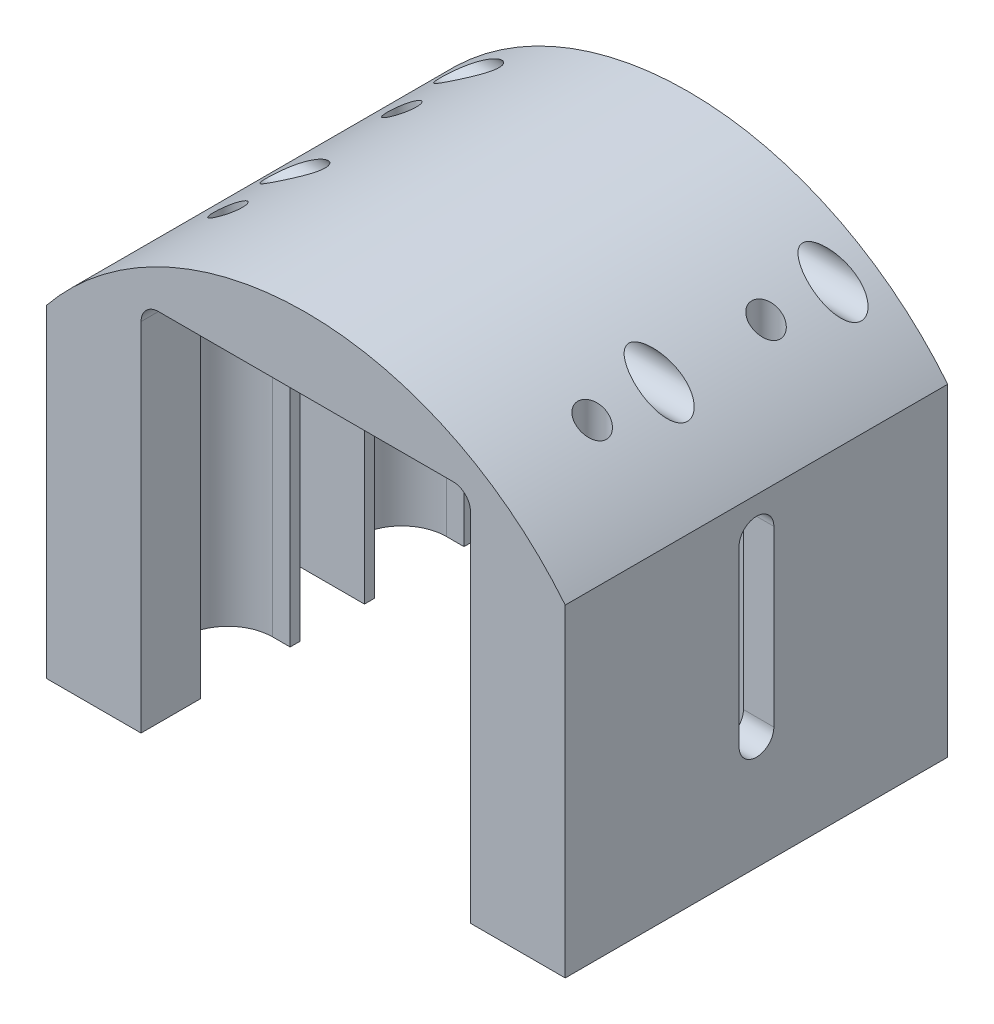
SolidWorks part; units mm, degrees
ref_plane "Front Plane" through (0, 0, 0) normal (0, 0, 1) x (1, 0, 0)
ref_plane "Top Plane" through (0, 0, 0) normal (0, 1, 0) x (1, 0, 0)
ref_plane "Right Plane" through (0, 0, 0) normal (1, 0, 0) x (0, 0, -1)
sketch "Sketch1" plane through (0, 0, 0) normal (0, 0, 1) x (1, 0, 0)
  line L0 (29.85, 24.1565) -> (29.85, -13)
  line L1 (29.85, -13) -> (-29.85, -13)
  line L2 (-29.85, -13) -> (-29.85, 24.1565)
  circle A0 centre (0, 0) radius 38.4
  dimension "D1" = 76.8
  dimension "D2" = 29.85
  dimension "D3" = 13
extrude "Boss-Extrude1" add sketch "Sketch1" along normal blind 44 contours L0 A0 L1 region at (0, 10.713, 0)
sketch "Sketch2" plane through (0, 0, 44) normal (0, 0, 1) x (1, 0, 0)
  line L0 (18.95, 0) -> (18.95, -33.3985)
  line L1 (-18.95, 0) -> (-18.95, -33.3985)
  line L2 (-18.95, 0) -> (-18.95, 28)
  line L3 (-16.95, 30) -> (16.95, 30)
  line L4 (18.95, 28) -> (18.95, 0)
  arc A1 (16.95, 30) -> (18.95, 28) centre (16.95, 28) cw
  arc A2 (29.85, 24.1565) -> (-29.85, 24.1565) centre (0, 0) ccw construction
  arc A4 (-18.95, -33.3985) -> (18.95, -33.3985) centre (0, 0) ccw
  arc A5 (-18.95, 28) -> (-16.95, 30) centre (-16.95, 28) cw
  point P1 (0, 30)
  dimension "D1" = 37.9
  dimension "D3" = 2
  dimension "D2" = 30
extrude "Cut-Extrude1" cut sketch "Sketch2" against normal through all contours L1 L0 | A5 L2 L4 A1 L3 region at (0, -3.4281, 44)
sketch "Sketch4" plane through (0, -13, 0) normal (0, -1, 0) x (-1, 0, 0)
  line L0 (18.95, 0) -> (18.95, -44) construction
  line L1 (18.95, -22) -> (-18.95, -22) construction
  line L4 (20.95, -6.85) -> (18.95, -6.85)
  line L5 (18.95, -6.85) -> (18.95, -17.15)
  line L6 (18.95, -17.15) -> (20.95, -17.15)
  line L7 (18.95, -26.85) -> (20.95, -26.85)
  line L8 (18.95, -37.15) -> (18.95, -26.85)
  line L9 (20.95, -37.15) -> (18.95, -37.15)
  line L10 (0, 0) -> (0, -41) construction
  line L11 (-18.95, 0) -> (-18.95, -44) construction
  line L12 (-20.95, -37.15) -> (-18.95, -37.15)
  line L13 (-18.95, -37.15) -> (-18.95, -26.85)
  line L14 (-18.95, -26.85) -> (-20.95, -26.85)
  line L15 (-18.95, -17.15) -> (-20.95, -17.15)
  line L16 (-18.95, -6.85) -> (-18.95, -17.15)
  line L17 (-20.95, -6.85) -> (-18.95, -6.85)
  line L18 (18.95, 0) -> (18.95, -44) construction
  line L19 (18.95, -18.3) -> (26.35, -18.3)
  line L20 (18.95, -18.3) -> (18.95, -25.7)
  line L21 (18.95, -25.7) -> (26.35, -25.7)
  line L22 (26.35, -18.3) -> (26.35, -25.7)
  line L23 (-18.95, -25.7) -> (-26.35, -25.7)
  line L24 (-26.35, -18.3) -> (-26.35, -25.7)
  line L25 (-18.95, -18.3) -> (-26.35, -18.3)
  line L26 (-18.95, -18.3) -> (-18.95, -25.7)
  line L29 (-18.95, -44) -> (-18.95, 0) construction
  line L30 (18.95, -44) -> (18.95, 0) construction
  circle A0 centre (20.95, -12) radius 5.15
  circle A2 centre (20.95, -32) radius 5.15
  circle A3 centre (-20.95, -32) radius 5.15
  circle A4 centre (-20.95, -12) radius 5.15
  point P6 (18.95, -20.5)
  point P7 (-18.95, -20.5)
  point P24 (-18.95, -35.5)
  point P43 (18.95, -22)
  point P49 (18.95, -5.5)
  point P52 (14.673, -25.5)
  point P53 (18.95, -25.5)
  line M24 (18.95, 0) -> (18.95, -44)
  dimension "D1" = 10.3
  dimension "D3" = 10
  dimension "D2" = 2
  dimension "D4" = 7.4
extrude "Cut-Extrude2" cut sketch "Sketch4" against normal offset from surface (38 mm away) 5 contours A2 L8 | A2 L8 | L9 A2 L8 | L8 A2 L7 | A0 L5 | A0 L5 L6 | A0 L4 L5 | A3 L13 | A3 L12 L13 | L13 A3 | A4 L16 | L16 A4 L15 | L17 A4 L16 | L26 L25 L24 L23 | L22 L19 L21 M24 | A3 L13 L14 region at (-19.446, -13, 6.9704) region at (-19.446, -13, 26.9704) region at (-22.65, -13, 22) region at (-22.1043, -13, 12) region at (-19.446, -13, 17.0296) region at (-22.1043, -13, 32) region at (-17.6497, -13, 32) region at (-19.446, -13, 37.0296) region at (19.446, -13, 37.0296) region at (22.1043, -13, 32) region at (19.446, -13, 26.9704) region at (17.6497, -13, 32) region at (19.446, -13, 17.0296) region at (22.1043, -13, 12) region at (19.446, -13, 6.9704) region at (22.65, -13, 22) up to face at (0, 30, 22)
sketch "Sketch6" plane through (0, 0, 0) normal (1, 0, 0) x (0, 0, -1)
  line L0 (-22, 20) -> (-22, 0) construction
  line L1 (-20, 20) -> (-20, 0)
  line L2 (-24, 20) -> (-24, 0)
  line L5 (-44, -13) -> (0, -13) construction
  arc A0 (-20, 20) -> (-24, 20) centre (-22, 20) ccw
  arc A1 (-24, 0) -> (-20, 0) centre (-22, 0) ccw
  point P2 (-22, 10)
  point P7 (0, 0)
  point P10 (-22, -13)
  dimension "D2" = 2
  dimension "D1" = 20
  dimension "D3" = 20
extrude "Cut-Extrude4" cut sketch "Sketch6" against normal through all both and the other way through all
sketch "Sketch7" plane through (29.85, 0, 0) normal (1, 0, 0) x (0, 0, -1)
  line L0 (0, 24.1565) -> (0, 38.4) construction
  line L1 (-0.8, 32) -> (-7.8, 32)
  line L2 (-20.8, 32) -> (-27.8, 32)
  circle A0 centre (-4.3, 32) radius 2.2
  circle A1 centre (-24.3, 32) radius 2.2
  circle A2 centre (-4.3, 32) radius 3.5
  circle A3 centre (-24.3, 32) radius 3.5
  dimension "D1" = 32
  dimension "D2" = 4.3
  dimension "D3" = 4.4
  dimension "D4" = 20
  dimension "D5" = 7
extrude "Boss-Extrude2" add sketch "Sketch7" against normal up to surface (48.8 mm away) from surface contours L2 A3 A1 | L1 A2 A0 region at (29.85, 28.5783, 4.3) region at (29.85, 28.5783, 24.3) up to face at (-18.95, 6.375, 22) starting at face at (18.95, 6.375, 22)
extrude "Cut-Extrude5" cut sketch "Sketch7<3>" against normal through all contours L2 A1 | L2 A1 | L1 A0 | L1 A0 region at (29.85, 31.0663, 4.3) region at (29.85, 32.9337, 4.3) region at (29.85, 31.0663, 24.3) region at (29.85, 32.9337, 24.3)
sketch "Sketch7<3>" plane through (29.85, 0, 0) normal (1, 0, 0) x (0, 0, -1) same geometry as "Sketch7"
sketch "Sketch8" plane through (0, 25, 0) normal (0, -1, 0) x (1, 0, 0)
  circle A0 centre (-20.95, 32) radius 1.65
  circle A1 centre (20.95, 32) radius 1.65
  circle A2 centre (20.95, 12) radius 1.65
  circle A3 centre (-20.95, 12) radius 1.65
  dimension "D1" = 3.3
extrude "Cut-Extrude6" cut sketch "Sketch8" against normal through all
sketch "Sketch9" plane through (0, -13, 0) normal (0, -1, 0) x (-1, 0, 0)
  line L0 (-29.85, 0) -> (-18.95, 0) construction
  line L1 (-18.95, -6.85) -> (-18.95, 0) construction
  circle A0 centre (-24.4, -3.425) radius 1.6
  circle A1 centre (-20.9, -1.925) radius 1.5
  circle A2 centre (-27.9, -4.925) radius 1.5
  point P5 (-24.4, 0)
  point P8 (-18.95, -3.425)
  point P12 (-20.6682, -1.8662)
  point P13 (-27.756, -5.0493)
  dimension "D1" = 3.2
  dimension "D2" = 3
  dimension "D3" = 3.5
  dimension "D4" = 3.5
  dimension "D5" = 1.5
  dimension "D6" = 1.5
extrude "Cut-Extrude7" [suppressed] cut sketch "Sketch9" against normal blind 7
equation "\"D6@Sketch9\"=\"D5@Sketch9\""
